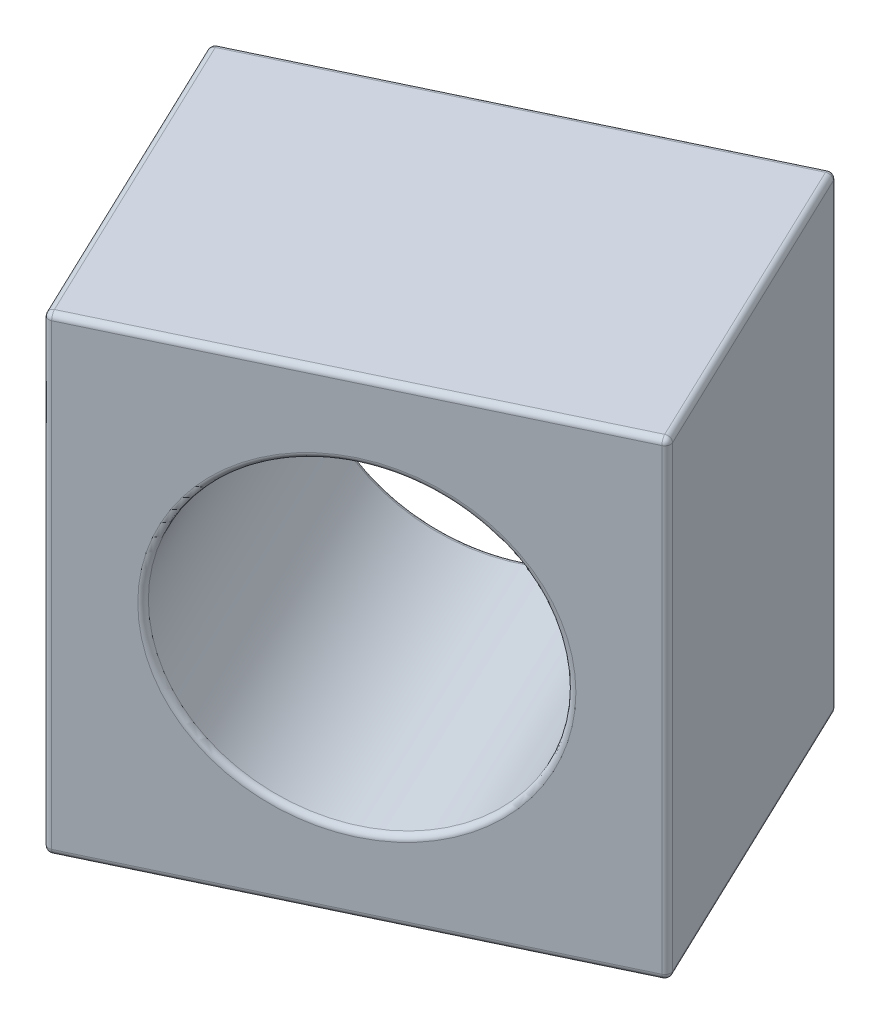
SolidWorks part; units mm, degrees
ref_plane "Front Plane" through (0, 0, 0) normal (0, 0, 1) x (1, 0, 0)
ref_plane "Top Plane" through (0, 0, 0) normal (0, 1, 0) x (1, 0, 0)
ref_plane "Right Plane" through (0, 0, 0) normal (1, 0, 0) x (0, 0, -1)
sketch "Sketch1" plane through (0, 0, 0) normal (0, 1, 0) x (1, 0, 0)
  line L0 (0, 0) -> (640, 0) construction
  line L1 (0, 0) -> (591.2829, 244.9174)
  line L2 (0, 0) -> (591.2829, -244.9174)
  line L3 (0, 0) -> (244.9174, -591.2829)
  line L4 (0, 0) -> (-244.9174, -591.2829)
  line L5 (0, 0) -> (-591.2829, -244.9174)
  line L6 (0, 0) -> (-591.2829, 244.9174)
  line L7 (0, 0) -> (-244.9174, 591.2829)
  line L8 (0, 0) -> (244.9174, 591.2829)
  line L9 (0, 145) -> (55, 145) construction
  line L10 (0, 0) -> (100, 0) construction
  line L11 (0, 0) -> (0, 145) construction
  line L14 (100, 0) -> (100, 145) construction
  circle A0 centre (0, 0) radius 640 construction
  point P15 (0, 0)
  dimension "D1" = 1280
  dimension "D2" = 22.5
  dimension "D4" = 145
  dimension "D5" = 100
  dimension "D6" = 55
  dimension "D3" = 8
sketch "Sketch2" plane through (0, 0, 0) normal (0, 1, 0) x (1, 0, 0)
  line L0 (-486.9956, 169.5033) -> (-66.9956, 169.5033) construction
  line L1 (-188.7141, -86.1278) -> (-188.7141, 241.8722) construction
  line L2 (525.6625, -1048.8053) -> (466.9027, -726.1115) construction
sketch "Sketch3" plane through (0, 0, 0) normal (0, 1, 0) x (1, 0, 0)
  line L0 (0, 0) -> (381.2468, 0) construction
  line L5 (0, 0) -> (0, 199.4415) construction
  line L6 (-10.2736, 158.9263) -> (10.2736, 158.9263)
  line L7 (10.2736, 158.9263) -> (13.1995, 163.9003)
  line L8 (13.1995, 163.9003) -> (45.5131, 148.2994)
  line L9 (45.5131, 148.2994) -> (66.2904, 80.9335)
  line L10 (66.2904, 80.9335) -> (73.8622, 80.9335)
  line L11 (73.8622, 80.9335) -> (86.8684, 42.4396)
  line L12 (86.8684, 42.4396) -> (86.8684, 30.0712)
  line L13 (86.8684, 30.0712) -> (81.3965, 24.5993)
  line L14 (81.3965, 24.5993) -> (81.3965, -24.5993)
  line L15 (-5.8349, 67.4929) -> (5.8349, 67.4929) construction
  line L16 (16.6008, 64.1674) -> (16.6008, 27.6557) construction
  line L17 (16.6008, 27.6557) -> (13.2646, 22.809) construction
  line L18 (13.2646, 22.809) -> (13.2646, -22.809) construction
  line L19 (5.8349, 128.0146) -> (5.8349, 107.4452)
  line L22 (5.8349, 107.4452) -> (9.2702, 107.4452)
  line L25 (9.2702, 107.4452) -> (10.663, 103.7163)
  line L26 (10.663, 103.7163) -> (20.7578, 101.0699)
  line L27 (20.7578, 101.0699) -> (32.199, 111.7601)
  line L28 (32.199, 111.7601) -> (32.199, 123.5038)
  line L29 (32.199, 123.5038) -> (24.9078, 123.5038)
  line L30 (24.9078, 123.5038) -> (13.8412, 132.5856)
  line L31 (13.8412, 132.5856) -> (9.2702, 132.5856)
  line L32 (9.2702, 132.5856) -> (5.8349, 128.0146)
  line L33 (41.9414, 39.7891) -> (51.4866, 54.1602)
  line L34 (51.4866, 54.1602) -> (55.4027, 54.1602)
  line L35 (55.4027, 54.1602) -> (58.1637, 51.3993)
  line L36 (58.1637, 51.3993) -> (58.1637, 43.1872)
  line L37 (58.1637, 43.1872) -> (66.3555, 28.462)
  line L38 (66.3555, 28.462) -> (66.3555, 24.0728)
  line L39 (66.3555, 24.0728) -> (62.2596, 17.9061)
  line L40 (62.2596, 17.9061) -> (47.8497, 18.1669)
  line L41 (47.8497, 18.1669) -> (41.9414, 27.1878)
  line L42 (41.9414, 27.1878) -> (41.9414, 39.7891)
  line L43 (-41.9414, 27.1878) -> (-41.9414, 39.7891)
  line L44 (-47.8497, 18.1669) -> (-41.9414, 27.1878)
  line L45 (-62.2596, 17.9061) -> (-47.8497, 18.1669)
  line L46 (-66.3555, 24.0728) -> (-62.2596, 17.9061)
  line L47 (-66.3555, 28.462) -> (-66.3555, 24.0728)
  line L48 (-58.1637, 43.1872) -> (-66.3555, 28.462)
  line L49 (-58.1637, 51.3993) -> (-58.1637, 43.1872)
  line L50 (-55.4027, 54.1602) -> (-58.1637, 51.3993)
  line L51 (-51.4866, 54.1602) -> (-55.4027, 54.1602)
  line L52 (-41.9414, 39.7891) -> (-51.4866, 54.1602)
  line L53 (-9.2702, 132.5856) -> (-5.8349, 128.0146)
  line L54 (-13.8412, 132.5856) -> (-9.2702, 132.5856)
  line L55 (-24.9078, 123.5038) -> (-13.8412, 132.5856)
  line L56 (-32.199, 123.5038) -> (-24.9078, 123.5038)
  line L57 (-32.199, 111.7601) -> (-32.199, 123.5038)
  line L58 (-20.7578, 101.0699) -> (-32.199, 111.7601)
  line L59 (-10.663, 103.7163) -> (-20.7578, 101.0699)
  line L60 (-9.2702, 107.4452) -> (-10.663, 103.7163)
  line L61 (-5.8349, 107.4452) -> (-9.2702, 107.4452)
  line L62 (-5.8349, 128.0146) -> (-5.8349, 107.4452)
  line L63 (-13.2646, 22.809) -> (-13.2646, -22.809) construction
  line L64 (-16.6008, 27.6557) -> (-13.2646, 22.809) construction
  line L65 (-16.6008, 64.1674) -> (-16.6008, 27.6557) construction
  line L66 (-81.3965, 24.5993) -> (-81.3965, -24.5993)
  line L67 (-86.8684, 30.0712) -> (-81.3965, 24.5993)
  line L68 (-86.8684, 42.4396) -> (-86.8684, 30.0712)
  line L69 (-73.8622, 80.9335) -> (-86.8684, 42.4396)
  line L70 (-66.2904, 80.9335) -> (-73.8622, 80.9335)
  line L71 (-45.5131, 148.2994) -> (-66.2904, 80.9335)
  line L72 (-13.1995, 163.9003) -> (-45.5131, 148.2994)
  line L73 (-10.2736, 158.9263) -> (-13.1995, 163.9003)
  line L74 (-10.2736, -158.9263) -> (-13.1995, -163.9003)
  line L75 (-13.1995, -163.9003) -> (-45.5131, -148.2994)
  line L76 (-45.5131, -148.2994) -> (-66.2904, -80.9335)
  line L77 (-66.2904, -80.9335) -> (-73.8622, -80.9335)
  line L78 (-73.8622, -80.9335) -> (-86.8684, -42.4396)
  line L79 (-86.8684, -42.4396) -> (-86.8684, -30.0712)
  line L80 (-86.8684, -30.0712) -> (-81.3965, -24.5993)
  line L81 (-16.6008, -64.1674) -> (-16.6008, -27.6557) construction
  line L82 (-16.6008, -27.6557) -> (-13.2646, -22.809) construction
  line L83 (-5.8349, -128.0146) -> (-5.8349, -107.4452)
  line L84 (-5.8349, -107.4452) -> (-9.2702, -107.4452)
  line L85 (-9.2702, -107.4452) -> (-10.663, -103.7163)
  line L86 (-10.663, -103.7163) -> (-20.7578, -101.0699)
  line L87 (-20.7578, -101.0699) -> (-32.199, -111.7601)
  line L88 (-32.199, -111.7601) -> (-32.199, -123.5038)
  line L89 (-32.199, -123.5038) -> (-24.9078, -123.5038)
  line L90 (-24.9078, -123.5038) -> (-13.8412, -132.5856)
  line L91 (-13.8412, -132.5856) -> (-9.2702, -132.5856)
  line L92 (-9.2702, -132.5856) -> (-5.8349, -128.0146)
  line L93 (-41.9414, -39.7891) -> (-51.4866, -54.1602)
  line L94 (-51.4866, -54.1602) -> (-55.4027, -54.1602)
  line L95 (-55.4027, -54.1602) -> (-58.1637, -51.3993)
  line L96 (-58.1637, -51.3993) -> (-58.1637, -43.1872)
  line L97 (-58.1637, -43.1872) -> (-66.3555, -28.462)
  line L98 (-66.3555, -28.462) -> (-66.3555, -24.0728)
  line L99 (-66.3555, -24.0728) -> (-62.2596, -17.9061)
  line L100 (-62.2596, -17.9061) -> (-47.8497, -18.1669)
  line L101 (-47.8497, -18.1669) -> (-41.9414, -27.1878)
  line L102 (-41.9414, -27.1878) -> (-41.9414, -39.7891)
  line L103 (41.9414, -27.1878) -> (41.9414, -39.7891)
  line L104 (47.8497, -18.1669) -> (41.9414, -27.1878)
  line L105 (62.2596, -17.9061) -> (47.8497, -18.1669)
  line L106 (66.3555, -24.0728) -> (62.2596, -17.9061)
  line L107 (66.3555, -28.462) -> (66.3555, -24.0728)
  line L108 (58.1637, -43.1872) -> (66.3555, -28.462)
  line L109 (58.1637, -51.3993) -> (58.1637, -43.1872)
  line L110 (55.4027, -54.1602) -> (58.1637, -51.3993)
  line L111 (51.4866, -54.1602) -> (55.4027, -54.1602)
  line L112 (41.9414, -39.7891) -> (51.4866, -54.1602)
  line L113 (9.2702, -132.5856) -> (5.8349, -128.0146)
  line L114 (13.8412, -132.5856) -> (9.2702, -132.5856)
  line L115 (24.9078, -123.5038) -> (13.8412, -132.5856)
  line L116 (32.199, -123.5038) -> (24.9078, -123.5038)
  line L117 (32.199, -111.7601) -> (32.199, -123.5038)
  line L118 (20.7578, -101.0699) -> (32.199, -111.7601)
  line L119 (10.663, -103.7163) -> (20.7578, -101.0699)
  line L120 (9.2702, -107.4452) -> (10.663, -103.7163)
  line L121 (5.8349, -107.4452) -> (9.2702, -107.4452)
  line L122 (5.8349, -128.0146) -> (5.8349, -107.4452)
  line L123 (16.6008, -27.6557) -> (13.2646, -22.809) construction
  line L124 (16.6008, -64.1674) -> (16.6008, -27.6557) construction
  line L125 (-5.8349, -67.4929) -> (5.8349, -67.4929) construction
  line L126 (86.8684, -30.0712) -> (81.3965, -24.5993)
  line L127 (86.8684, -42.4396) -> (86.8684, -30.0712)
  line L128 (73.8622, -80.9335) -> (86.8684, -42.4396)
  line L129 (66.2904, -80.9335) -> (73.8622, -80.9335)
  line L130 (45.5131, -148.2994) -> (66.2904, -80.9335)
  line L131 (13.1995, -163.9003) -> (45.5131, -148.2994)
  line L132 (10.2736, -158.9263) -> (13.1995, -163.9003)
  line L133 (-10.2736, -158.9263) -> (10.2736, -158.9263)
  line L134 (-5.3457, 68.4929) -> (5.3457, 68.4929)
  line L135 (17.6008, 64.1674) -> (17.6008, 27.3448)
  line L136 (17.6008, 27.3448) -> (14.2646, 22.498)
  line L137 (14.2646, 22.498) -> (14.2646, -22.498)
  line L138 (-17.6008, 64.1674) -> (-17.6008, 27.3448)
  line L139 (-17.6008, 27.3448) -> (-14.2646, 22.498)
  line L140 (-5.3457, 68.4929) -> (5.3457, 68.4929) construction
  line L141 (14.2646, 22.498) -> (14.2646, -22.498) construction
  line L142 (17.6008, -27.3448) -> (14.2646, -22.498) construction
  line L143 (17.6008, -64.1674) -> (17.6008, -27.3448) construction
  line L144 (-14.2646, 22.498) -> (-14.2646, -22.498)
  line L145 (17.6008, -64.1674) -> (17.6008, -27.3448)
  line L146 (17.6008, -27.3448) -> (14.2646, -22.498)
  line L147 (-17.6008, -27.3448) -> (-14.2646, -22.498)
  line L148 (-17.6008, -64.1674) -> (-17.6008, -27.3448)
  line L149 (-5.3457, -68.4929) -> (5.3457, -68.4929)
  arc A0 (5.8349, 67.4929) -> (16.6008, 64.0252) centre (10.663, 64.0364) cw construction
  arc A5 (-5.8349, 67.4929) -> (-16.6008, 64.0252) centre (-10.663, 64.0364) ccw construction
  arc A6 (-5.8349, -67.4929) -> (-16.6008, -64.0252) centre (-10.663, -64.0364) cw construction
  arc A7 (5.8349, -67.4929) -> (16.6008, -64.0252) centre (10.663, -64.0364) ccw construction
  arc A8 (-5.3457, 68.4929) -> (-17.6008, 64.0234) centre (-10.663, 64.0364) ccw
  arc A9 (5.3457, 68.4929) -> (17.6008, 64.0234) centre (10.663, 64.0364) cw
  arc A10 (-5.3457, 68.4929) -> (-17.6008, 64.0234) centre (-10.663, 64.0364) ccw construction
  arc A11 (5.3457, -68.4929) -> (17.6008, -64.0234) centre (10.663, -64.0364) ccw
  arc A12 (-5.3457, -68.4929) -> (-17.6008, -64.0234) centre (-10.663, -64.0364) cw
  ellipse E0 centre (11.3851, 149.6854) end of major axis (12.0553, 155.2702) minor radius 3.0047
  ellipse E1 centre (33.6925, 82.363) end of major axis (41.1096, 88.3895) minor radius 4.3287
  ellipse E2 centre (44.8955, 74.0187) end of major axis (51.4866, 79.374) minor radius 4.6847
  ellipse E3 centre (66.3555, 66.447) end of major axis (67.1471, 72.2416) minor radius 3.5711
  ellipse E4 centre (-66.3555, 66.447) end of major axis (-67.1471, 72.2416) minor radius 3.5711
  ellipse E5 centre (-44.8955, 74.0187) end of major axis (-51.4866, 79.374) minor radius 4.6847
  ellipse E6 centre (-33.6925, 82.363) end of major axis (-41.1096, 88.3895) minor radius 4.3287
  ellipse E7 centre (-11.3851, 149.6854) end of major axis (-12.0553, 155.2702) minor radius 3.0047
  ellipse E8 centre (-11.3851, -149.6854) end of major axis (-12.0553, -155.2702) minor radius 3.0047
  ellipse E9 centre (-33.6925, -82.363) end of major axis (-41.1096, -88.3895) minor radius 4.3287
  ellipse E10 centre (-44.8955, -74.0187) end of major axis (-51.4866, -79.374) minor radius 4.6847
  ellipse E11 centre (-66.3555, -66.447) end of major axis (-67.1471, -72.2416) minor radius 3.5711
  ellipse E12 centre (66.3555, -66.447) end of major axis (67.1471, -72.2416) minor radius 3.5711
  ellipse E13 centre (44.8955, -74.0187) end of major axis (51.4866, -79.374) minor radius 4.6847
  ellipse E14 centre (33.6925, -82.363) end of major axis (41.1096, -88.3895) minor radius 4.3287
  ellipse E15 centre (11.3851, -149.6854) end of major axis (12.0553, -155.2702) minor radius 3.0047
  point P117 (0, 67.4929)
  point P126 (0, 158.9263)
  point P180 (0, -158.9263)
  point P181 (0, -67.4929)
  point P190 (-81.3965, 0)
  point P193 (-13.2646, 0)
  point P234 (13.2646, 0)
  point P237 (81.3965, 0)
  point P261 (0, 68.4929)
  point P271 (14.2646, 0)
  point P274 (-14.2646, 0)
  dimension "D1" = 1
sketch "Sketch4" plane through (0, 0, 0) normal (0, 1, 0) x (1, 0, 0)
  line L0 (0, 0) -> (81.2255, 0) construction
  line L1 (0, 0) -> (0, 97.3086) construction
  line L2 (0, 0) -> (0, 199.4415) construction
  line L3 (-10.1399, 86.6928) -> (10.1399, 86.6928)
  line L4 (10.1399, 86.6928) -> (16.0235, 80.8091)
  line L5 (16.0235, 80.8091) -> (23.9736, 57.3032)
  line L6 (23.9736, 57.3032) -> (23.9736, 47.8894)
  line L7 (23.9736, 47.8894) -> (21.6776, 47.8894)
  line L8 (21.6776, 47.8894) -> (21.6776, 27.2256)
  line L9 (21.6776, 27.2256) -> (27.5382, 22.1416)
  line L10 (27.5382, 22.1416) -> (27.5382, 14.9676)
  line L11 (27.5382, 14.9676) -> (23.9736, 10.8585)
  line L12 (23.9736, 10.8585) -> (23.9736, -10.8585)
  line L13 (-23.9736, 10.8585) -> (-23.9736, -10.8585)
  line L14 (-27.5382, 14.9676) -> (-23.9736, 10.8585)
  line L15 (-27.5382, 22.1416) -> (-27.5382, 14.9676)
  line L16 (-21.6776, 27.2256) -> (-27.5382, 22.1416)
  line L17 (-21.6776, 47.8894) -> (-21.6776, 27.2256)
  line L18 (-23.9736, 47.8894) -> (-21.6776, 47.8894)
  line L19 (-23.9736, 57.3032) -> (-23.9736, 47.8894)
  line L20 (-16.0235, 80.8091) -> (-23.9736, 57.3032)
  line L21 (-10.1399, 86.6928) -> (-16.0235, 80.8091)
  line L22 (-10.1399, -86.6928) -> (-16.0235, -80.8091)
  line L23 (-16.0235, -80.8091) -> (-23.9736, -57.3032)
  line L24 (-23.9736, -57.3032) -> (-23.9736, -47.8894)
  line L25 (-23.9736, -47.8894) -> (-21.6776, -47.8894)
  line L26 (-21.6776, -47.8894) -> (-21.6776, -27.2256)
  line L27 (-21.6776, -27.2256) -> (-27.5382, -22.1416)
  line L28 (-27.5382, -22.1416) -> (-27.5382, -14.9676)
  line L29 (-27.5382, -14.9676) -> (-23.9736, -10.8585)
  line L30 (27.5382, -14.9676) -> (23.9736, -10.8585)
  line L31 (27.5382, -22.1416) -> (27.5382, -14.9676)
  line L32 (21.6776, -27.2256) -> (27.5382, -22.1416)
  line L33 (21.6776, -47.8894) -> (21.6776, -27.2256)
  line L34 (23.9736, -47.8894) -> (21.6776, -47.8894)
  line L35 (23.9736, -57.3032) -> (23.9736, -47.8894)
  line L36 (16.0235, -80.8091) -> (23.9736, -57.3032)
  line L37 (10.1399, -86.6928) -> (16.0235, -80.8091)
  line L38 (-10.1399, -86.6928) -> (10.1399, -86.6928)
  point P3 (0, -86.6928)
  point P27 (0, 86.6928)
  point P37 (-23.9736, 0)
  point P38 (23.9736, 0)
sketch "Sketch5" plane through (0, 0, 0) normal (0, 1, 0) x (1, 0, 0)
  line L0 (0, 68.4929) -> (0, 86.6928) construction
  line L1 (15.4511, 110) -> (223.3697, 546.0887)
  line L2 (0, 0) -> (0, 251.8084) construction
  line L3 (0, 110) -> (47.9221, 110) construction
  line L5 (244.9174, 616.9519) -> (262.4572, 609.0616) construction
  line L6 (262.4572, 609.0616) -> (269.1565, 599.6825) construction
  line L7 (269.1565, 599.6825) -> (256.4381, 571.4103) construction
  line L8 (256.4381, 571.4103) -> (244.9174, 563.1812) construction
  line L9 (244.9174, 563.1812) -> (221.08, 517.0826) construction
  line L10 (221.08, 517.0826) -> (201.6817, 527.1134) construction
  line L11 (201.6817, 527.1134) -> (221.6088, 571.4103) construction
  line L12 (221.6088, 571.4103) -> (218.2415, 584.6462) construction
  line L13 (218.2415, 584.6462) -> (232.4366, 616.2011) construction
  line L14 (232.4366, 616.2011) -> (244.9174, 616.9519) construction
  line L15 (244.9174, 591.2829) -> (309.3694, 564.586) construction
  line L16 (269.6266, 526.9284) -> (173.6132, 566.6985) construction
  line L18 (0, 0) -> (107.3069, 0) construction
  dimension "D1" = 110
  dimension "D2" = 50
sketch "Sketch6" plane through (0, 0, 0) normal (0, 1, 0) x (1, 0, 0)
  line L1 (27.9119, 24.7148) -> (544.6401, 226.6863)
  circle A0 centre (0, 0) radius 640 construction
  circle A1 centre (0, 0) radius 640 construction
  circle A3 centre (0, 0) radius 589.9318 construction
  dimension "D1" = 50.0682
sketch "Sketch19" plane through (0, 0, 0) normal (0, 1, 0) x (1, 0, 0)
  line L0 (128.4599, 309.2664) -> (271.805, 137.4916) construction
  line L1 (128.4599, 309.2664) -> (95.7387, 324.8672) construction
  line L2 (128.4599, 309.2664) -> (131.8448, 307.6525) construction
  line L3 (-2.602, 118.6074) -> (205.3166, 554.696)
  line L4 (-2.602, 118.6074) -> (205.3166, 554.696) construction
  line L5 (26.7343, 104.6204) -> (234.6528, 540.7091)
  line L6 (26.7343, 104.6204) -> (234.6528, 540.7091) construction
  line L7 (4.1679, 115.3796) -> (212.0865, 551.4683)
  line L8 (4.1679, 115.3796) -> (212.0865, 551.4683) construction
  line L9 (20.631, 43.3425) -> (537.3592, 245.3139)
  line L10 (32.4624, 13.0726) -> (549.1907, 215.044)
  line L11 (32.4624, 13.0726) -> (549.1907, 215.044) construction
  line L12 (23.3613, 36.3571) -> (540.0895, 238.3286)
  line L13 (23.3613, 36.3571) -> (540.0895, 238.3286) construction
  line L14 (20.631, 43.3425) -> (537.3592, 245.3139) construction
  line L15 (30.1192, 103.0065) -> (238.0378, 539.0952)
  line L16 (30.1192, 103.0065) -> (238.0378, 539.0952) construction
  line L17 (134.9154, 322.8062) -> (138.3004, 321.1923)
  line L18 (134.9154, 322.8062) -> (102.1942, 338.407)
  line L19 (122.0044, 295.7266) -> (125.3893, 294.1127)
  line L20 (122.0044, 295.7266) -> (89.2832, 311.3274)
  line L21 (89.2832, 311.3274) -> (102.1942, 338.407)
  line L22 (21.9961, 39.8498) -> (538.7244, 241.8213)
  line L23 (21.9961, 39.8498) -> (538.7244, 241.8213) construction
  line L24 (33.5042, 101.3926) -> (241.4227, 537.4813)
  line L25 (33.5042, 101.3926) -> (241.4227, 537.4813) construction
  line L26 (138.3004, 321.1923) -> (125.3893, 294.1127)
  dimension "D7" = 15
  dimension "D1" = 12.5
  dimension "D2" = 12.5
  dimension "D3" = 12.5
  dimension "D4" = 12.5
  dimension "D5" = 16.25
  dimension "D6" = 20
  dimension "D8" = 16.25
  dimension "D9" = 15
  dimension "D10" = 20
  dimension "D11" = 20
extrude "Boss-Extrude1" add sketch "Sketch19" along normal blind 20 and the other way blind 20
sweep "Cut-Sweep1" cut path "Sketch5" circular profile diameter 27 parameters "D3"=27
sketch "Sketch33" plane through (0, 0, 0) normal (0, 1, 0) x (1, 0, 0)
  line L0 (128.4599, 309.2664) -> (271.805, 137.4916)
sweep "Cut-Sweep2" cut path "Sketch33" circular profile diameter 12 parameters "D3"=12
fillet "Fillet1" radius 0.5 15 edges at (108.0615, 0, -335.6096) (120.2473, -20, -329.7996) (107.3362, -20, -302.72) (119.5221, 0, -296.9101) (131.8448, -20, -307.6525) (125.3893, 0, -294.1127) (138.3004, 0, -321.1923) (128.2623, 0, -300.1385) (131.8448, 20, -307.6525) (107.3362, 20, -302.72) (120.2473, 20, -329.7996) (95.7387, -20, -324.8672) (102.1942, 0, -338.407) (95.7387, 20, -324.8672) (89.2832, 0, -311.3274)
mirror "Mirror2" about plane through (0, 0, 0) normal (1, 0, 0) of bodies 111 112
delete or keep bodies "Body-Delete/Keep 1" type delete bodies bodies 111
